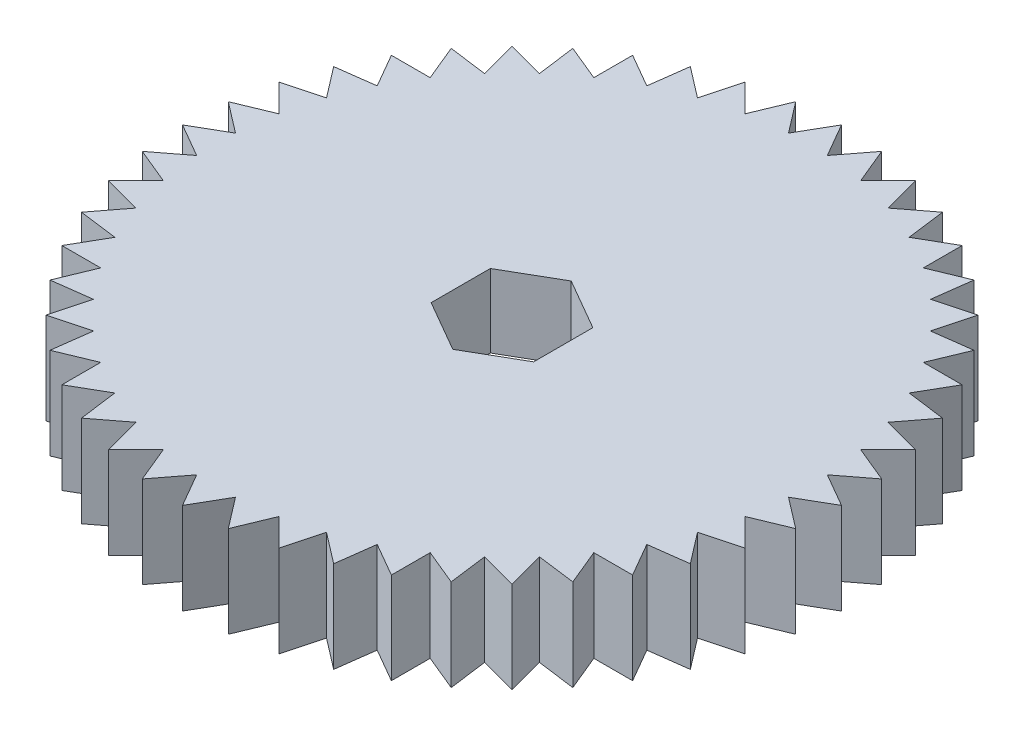
SolidWorks part; units mm, degrees
ref_plane "Front Plane" through (0, 0, 0) normal (0, 0, 1) x (1, 0, 0)
ref_plane "Top Plane" through (0, 0, 0) normal (0, 1, 0) x (1, 0, 0)
ref_plane "Right Plane" through (0, 0, 0) normal (1, 0, 0) x (0, 0, -1)
sketch "Sketch1" plane through (0, 0, 0) normal (0, 1, 0) x (1, 0, 0)
  circle A1 centre (0, 0) radius 19.05
  dimension "D2" = 38.1
extrude "Boss-Extrude1" add sketch "Sketch1" along normal blind 5.08
sketch "Sketch3" plane through (0, 5.08, 0) normal (0, 1, 0) x (1, 0, 0)
  line L0 (0, 0) -> (0, 22.86) construction
  line L1 (0, 22.86) -> (2.2787, 18.9132)
  line L2 (0, 22.86) -> (-2.2787, 18.9132)
  line L3 (2.2787, 18.9132) -> (-2.2787, 18.9132)
  circle A0 centre (0, 0) radius 19.05 construction
  dimension "D1" = 22.86
  dimension "D2" = 30
  dimension "D3" = 30
extrude "Boss-Extrude3" add sketch "Sketch3" against normal blind 6.35
ref_axis "Axis1" through (0, -0.127, 0) along (0, 1, 0)
pattern_circular "CirPattern1" count 48 every 7.5 about axis through (0, -0.127, 0) along (0, 1, 0) of "Boss-Extrude3"
sketch "Sketch6" plane through (0, 0, 0) normal (0, -1, 0) x (1, 0, 0)
  line L1 (0, -4.1061) -> (3.556, -2.0531)
  line L2 (3.556, -2.0531) -> (3.556, 2.0531)
  line L3 (3.556, 2.0531) -> (0, 4.1061)
  line L4 (0, 4.1061) -> (-3.556, 2.0531)
  line L5 (-3.556, 2.0531) -> (-3.556, -2.0531)
  line L6 (-3.556, -2.0531) -> (0, -4.1061)
  circle A0 centre (0, 0) radius 3.556 construction
  dimension "D1" = 7.112
extrude "Cut-Extrude1" cut sketch "Sketch6" against normal through all
